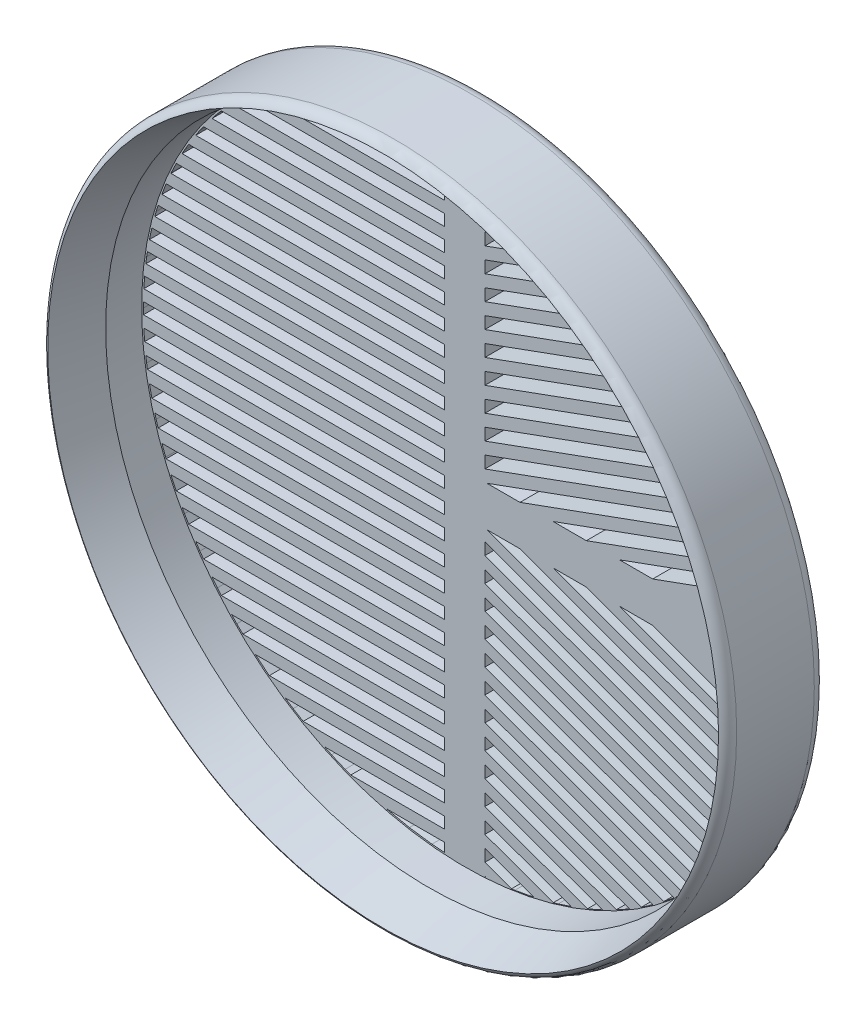
SolidWorks part; units mm, degrees
ref_plane "Front Plane" through (0, 0, 0) normal (0, 0, 1) x (1, 0, 0)
ref_plane "Top Plane" through (0, 0, 0) normal (0, 1, 0) x (1, 0, 0)
ref_plane "Right Plane" through (0, 0, 0) normal (1, 0, 0) x (0, 0, -1)
sketch "Model" plane through (0, 0, 0) normal (0, 0, 1) x (1, 0, 0)
  line L0 (75.5028, -6.5152) -> (75.5028, -6.5734)
  line L1 (75.5028, -6.5734) -> (75.6328, -6.5625)
  line L2 (75.6328, -6.5625) -> (75.5028, -6.5152)
  line L3 (60.2356, -5.0803) -> (60.3368, -5.1079)
  line L4 (60.3368, -5.1079) -> (63.7612, -5.8295)
  line L5 (63.7612, -5.8295) -> (67.2675, -6.313)
  line L6 (67.2675, -6.313) -> (69.2528, -6.4649)
  line L7 (69.2528, -6.4649) -> (69.2528, -5.0803)
  line L8 (69.2528, -5.0803) -> (60.2356, -5.0803)
  line L9 (75.5028, -2.761) -> (75.5028, -4.6381)
  line L10 (75.5028, -4.6381) -> (79.6342, -6.1418)
  line L11 (79.6342, -6.1418) -> (80.1696, -6.0715)
  line L12 (80.1696, -6.0715) -> (82.4518, -5.6634)
  line L13 (82.4518, -5.6634) -> (83.0833, -5.5201)
  line L14 (83.0833, -5.5201) -> (75.5028, -2.761)
  line L15 (50.5682, -1.5526) -> (51.6711, -2.0865)
  line L16 (51.6711, -2.0865) -> (53.7681, -2.9857)
  line L17 (53.7681, -2.9857) -> (54.6495, -3.3165)
  line L18 (54.6495, -3.3165) -> (69.2528, -3.3165)
  line L19 (69.2528, -3.3165) -> (69.2528, -1.5526)
  line L20 (69.2528, -1.5526) -> (50.5682, -1.5526)
  line L21 (75.5028, 0.9932) -> (75.5028, -0.8839)
  line L22 (75.5028, -0.8839) -> (86.1399, -4.7555)
  line L23 (86.1399, -4.7555) -> (86.9019, -4.5452)
  line L24 (86.9019, -4.5452) -> (88.9156, -3.8887)
  line L25 (88.9156, -3.8887) -> (75.5028, 0.9932)
  line L26 (44.4531, 1.9752) -> (45.6937, 1.1501)
  line L27 (45.6937, 1.1501) -> (47.2535, 0.2113)
  line L28 (47.2535, 0.2113) -> (69.2528, 0.2113)
  line L29 (69.2528, 0.2113) -> (69.2528, 1.9752)
  line L30 (69.2528, 1.9752) -> (44.4531, 1.9752)
  line L31 (75.5028, 4.7474) -> (75.5028, 2.8703)
  line L32 (75.5028, 2.8703) -> (91.4397, -2.9303)
  line L33 (91.4397, -2.9303) -> (93.2537, -2.1499)
  line L34 (93.2537, -2.1499) -> (93.7679, -1.9006)
  line L35 (93.7679, -1.9006) -> (75.5028, 4.7474)
  line L36 (39.8298, 5.503) -> (40.2413, 5.1409)
  line L37 (40.2413, 5.1409) -> (41.9862, 3.7391)
  line L38 (41.9862, 3.7391) -> (69.2528, 3.7391)
  line L39 (69.2528, 3.7391) -> (69.2528, 5.503)
  line L40 (69.2528, 5.503) -> (39.8298, 5.503)
  line L41 (75.5028, 8.5015) -> (75.5028, 6.6245)
  line L42 (75.5028, 6.6245) -> (95.9351, -0.8123)
  line L43 (95.9351, -0.8123) -> (97.244, -0.1032)
  line L44 (97.244, -0.1032) -> (97.9606, 0.3276)
  line L45 (97.9606, 0.3276) -> (75.5028, 8.5015)
  line L46 (36.1298, 9.0308) -> (36.9324, 8.1861)
  line L47 (36.9324, 8.1861) -> (37.8874, 7.2669)
  line L48 (37.8874, 7.2669) -> (69.2528, 7.2669)
  line L49 (69.2528, 7.2669) -> (69.2528, 9.0308)
  line L50 (69.2528, 9.0308) -> (36.1298, 9.0308)
  line L51 (75.5028, 12.2557) -> (75.5028, 10.3786)
  line L52 (75.5028, 10.3786) -> (99.8601, 1.5133)
  line L53 (99.8601, 1.5133) -> (101.0159, 2.2804)
  line L54 (101.0159, 2.2804) -> (101.6462, 2.7403)
  line L55 (101.6462, 2.7403) -> (75.5028, 12.2557)
  line L56 (33.081, 12.5585) -> (33.9086, 11.5147)
  line L57 (33.9086, 11.5147) -> (34.5338, 10.7947)
  line L58 (34.5338, 10.7947) -> (69.2528, 10.7947)
  line L59 (69.2528, 10.7947) -> (69.2528, 12.5585)
  line L60 (69.2528, 12.5585) -> (33.081, 12.5585)
  line L61 (75.5028, 16.0099) -> (75.5028, 14.1328)
  line L62 (75.5028, 14.1328) -> (103.3293, 4.0048)
  line L63 (103.3293, 4.0048) -> (104.5495, 4.9811)
  line L64 (104.5495, 4.9811) -> (104.918, 5.3037)
  line L65 (104.918, 5.3037) -> (75.5028, 16.0099)
  line L66 (30.5476, 16.0863) -> (31.1904, 15.106)
  line L67 (31.1904, 15.106) -> (31.7563, 14.3224)
  line L68 (31.7563, 14.3224) -> (69.2528, 14.3224)
  line L69 (69.2528, 14.3224) -> (69.2528, 16.0863)
  line L70 (69.2528, 16.0863) -> (30.5476, 16.0863)
  line L71 (28.4389, 19.6141) -> (28.7986, 18.9395)
  line L72 (28.7986, 18.9395) -> (29.4446, 17.8502)
  line L73 (29.4446, 17.8502) -> (69.2528, 17.8502)
  line L74 (69.2528, 17.8502) -> (69.2528, 19.6141)
  line L75 (69.2528, 19.6141) -> (28.4389, 19.6141)
  line L76 (75.5028, 19.7641) -> (75.5028, 17.887)
  line L77 (75.5028, 17.887) -> (106.4195, 6.6343)
  line L78 (106.4195, 6.6343) -> (107.8253, 7.9792)
  line L79 (107.8253, 7.9792) -> (107.8398, 7.9944)
  line L80 (107.8398, 7.9944) -> (75.5028, 19.7641)
  line L81 (26.6919, 23.1419) -> (26.7539, 22.9945)
  line L82 (26.7539, 22.9945) -> (27.5234, 21.378)
  line L83 (27.5234, 21.378) -> (69.2528, 21.378)
  line L84 (69.2528, 21.378) -> (69.2528, 23.1419)
  line L85 (69.2528, 23.1419) -> (26.6919, 23.1419)
  line L86 (75.5028, 23.5183) -> (75.5028, 21.6412)
  line L87 (75.5028, 21.6412) -> (109.1719, 9.3867)
  line L88 (109.1719, 9.3867) -> (109.3602, 9.5836)
  line L89 (109.3602, 9.5836) -> (110.4302, 10.8058)
  line L90 (110.4302, 10.8058) -> (75.5028, 23.5183)
  line L91 (25.2904, 26.6697) -> (25.8682, 25.0985)
  line L92 (25.8682, 25.0985) -> (25.9493, 24.9058)
  line L93 (25.9493, 24.9058) -> (69.2528, 24.9058)
  line L94 (69.2528, 24.9058) -> (69.2528, 26.6697)
  line L95 (69.2528, 26.6697) -> (25.2904, 26.6697)
  line L96 (75.5028, 27.2725) -> (75.5028, 25.3954)
  line L97 (75.5028, 25.3954) -> (111.6195, 12.25)
  line L98 (111.6195, 12.25) -> (112.2121, 12.9907)
  line L99 (112.2121, 12.9907) -> (112.7429, 13.7182)
  line L100 (112.7429, 13.7182) -> (75.5028, 27.2725)
  line L101 (24.1835, 30.1974) -> (24.3828, 29.4467)
  line L102 (24.3828, 29.4467) -> (24.703, 28.4335)
  line L103 (24.703, 28.4335) -> (69.2528, 28.4335)
  line L104 (69.2528, 28.4335) -> (69.2528, 30.1974)
  line L105 (69.2528, 30.1974) -> (24.1835, 30.1974)
  line L106 (75.5028, 31.0266) -> (75.5028, 29.1496)
  line L107 (75.5028, 29.1496) -> (113.8033, 15.2093)
  line L108 (113.8033, 15.2093) -> (114.7567, 16.6459)
  line L109 (114.7567, 16.6459) -> (114.8028, 16.7226)
  line L110 (114.8028, 16.7226) -> (75.5028, 31.0266)
  line L111 (23.348, 33.7252) -> (23.7289, 31.9613)
  line L112 (23.7289, 31.9613) -> (69.2528, 31.9613)
  line L113 (69.2528, 31.9613) -> (69.2528, 33.7252)
  line L114 (69.2528, 33.7252) -> (23.348, 33.7252)
  line L115 (75.5028, 34.7808) -> (75.5028, 32.9037)
  line L116 (75.5028, 32.9037) -> (115.7287, 18.2627)
  line L117 (115.7287, 18.2627) -> (115.9076, 18.5604)
  line L118 (115.9076, 18.5604) -> (116.5928, 19.8253)
  line L119 (116.5928, 19.8253) -> (75.5028, 34.7808)
  line L120 (22.7933, 37.253) -> (22.909, 36.2807)
  line L121 (22.909, 36.2807) -> (23.0414, 35.4891)
  line L122 (23.0414, 35.4891) -> (69.2528, 35.4891)
  line L123 (69.2528, 35.4891) -> (69.2528, 37.253)
  line L124 (69.2528, 37.253) -> (22.7933, 37.253)
  line L125 (75.5028, 38.535) -> (75.5028, 36.6579)
  line L126 (75.5028, 36.6579) -> (117.4005, 21.4084)
  line L127 (117.4005, 21.4084) -> (117.9543, 22.5507)
  line L128 (117.9543, 22.5507) -> (118.1527, 23.0117)
  line L129 (118.1527, 23.0117) -> (75.5028, 38.535)
  line L130 (96.4355, 40.3016) -> (121.0145, 31.3556)
  line L131 (121.0145, 31.3556) -> (121.4081, 33.0894)
  line L132 (121.4081, 33.0894) -> (101.5928, 40.3016)
  line L133 (101.5928, 40.3016) -> (96.4355, 40.3016)
  line L134 (86.121, 40.3016) -> (120.0409, 27.9557)
  line L135 (120.0409, 27.9557) -> (120.3496, 28.9025)
  line L136 (120.3496, 28.9025) -> (120.5548, 29.6458)
  line L137 (120.5548, 29.6458) -> (91.2782, 40.3016)
  line L138 (91.2782, 40.3016) -> (86.121, 40.3016)
  line L139 (75.8064, 40.3016) -> (118.8502, 24.6349)
  line L140 (118.8502, 24.6349) -> (119.473, 26.2854)
  line L141 (119.473, 26.2854) -> (80.9637, 40.3016)
  line L142 (80.9637, 40.3016) -> (75.8064, 40.3016)
  line L143 (22.476, 40.7808) -> (22.6017, 39.0169)
  line L144 (22.6017, 39.0169) -> (69.2528, 39.0169)
  line L145 (69.2528, 39.0169) -> (69.2528, 40.7808)
  line L146 (69.2528, 40.7808) -> (22.476, 40.7808)
  line L147 (22.4231, 44.3085) -> (22.4022, 43.4266)
  line L148 (22.4022, 43.4266) -> (22.4231, 42.5447)
  line L149 (22.4231, 42.5447) -> (69.2528, 42.5447)
  line L150 (69.2528, 42.5447) -> (69.2528, 44.3085)
  line L151 (69.2528, 44.3085) -> (22.4231, 44.3085)
  line L152 (22.6017, 47.8363) -> (22.476, 46.0724)
  line L153 (22.476, 46.0724) -> (69.2528, 46.0724)
  line L154 (69.2528, 46.0724) -> (69.2528, 47.8363)
  line L155 (69.2528, 47.8363) -> (22.6017, 47.8363)
  line L156 (23.0414, 51.3641) -> (22.909, 50.5725)
  line L157 (22.909, 50.5725) -> (22.7933, 49.6002)
  line L158 (22.7933, 49.6002) -> (69.2528, 49.6002)
  line L159 (69.2528, 49.6002) -> (69.2528, 51.3641)
  line L160 (69.2528, 51.3641) -> (23.0414, 51.3641)
  line L161 (23.7289, 54.8919) -> (23.348, 53.128)
  line L162 (23.348, 53.128) -> (69.2528, 53.128)
  line L163 (69.2528, 53.128) -> (69.2528, 54.8919)
  line L164 (69.2528, 54.8919) -> (23.7289, 54.8919)
  line L165 (121.0145, 55.4976) -> (96.4355, 46.5516)
  line L166 (96.4355, 46.5516) -> (101.5928, 46.5516)
  line L167 (101.5928, 46.5516) -> (121.4081, 53.7638)
  line L168 (121.4081, 53.7638) -> (121.0145, 55.4976)
  line L169 (24.703, 58.4197) -> (24.3828, 57.4065)
  line L170 (24.3828, 57.4065) -> (24.1835, 56.6558)
  line L171 (24.1835, 56.6558) -> (69.2528, 56.6558)
  line L172 (69.2528, 56.6558) -> (69.2528, 58.4197)
  line L173 (69.2528, 58.4197) -> (24.703, 58.4197)
  line L174 (120.0409, 58.8975) -> (86.121, 46.5516)
  line L175 (86.121, 46.5516) -> (91.2782, 46.5516)
  line L176 (91.2782, 46.5516) -> (120.5548, 57.2074)
  line L177 (120.5548, 57.2074) -> (120.3496, 57.9507)
  line L178 (120.3496, 57.9507) -> (120.0409, 58.8975)
  line L179 (25.9493, 61.9474) -> (25.8682, 61.7547)
  line L180 (25.8682, 61.7547) -> (25.2904, 60.1835)
  line L181 (25.2904, 60.1835) -> (69.2528, 60.1835)
  line L182 (69.2528, 60.1835) -> (69.2528, 61.9474)
  line L183 (69.2528, 61.9474) -> (25.9493, 61.9474)
  line L184 (118.8502, 62.2183) -> (75.8064, 46.5516)
  line L185 (75.8064, 46.5516) -> (80.9637, 46.5516)
  line L186 (80.9637, 46.5516) -> (119.473, 60.5678)
  line L187 (119.473, 60.5678) -> (118.8502, 62.2183)
  line L188 (117.4005, 65.4448) -> (75.5028, 50.1953)
  line L189 (75.5028, 50.1953) -> (75.5028, 48.3182)
  line L190 (75.5028, 48.3182) -> (118.1527, 63.8415)
  line L191 (118.1527, 63.8415) -> (117.9543, 64.3025)
  line L192 (117.9543, 64.3025) -> (117.4005, 65.4448)
  line L193 (27.5234, 65.4752) -> (26.7539, 63.8587)
  line L194 (26.7539, 63.8587) -> (26.6919, 63.7113)
  line L195 (26.6919, 63.7113) -> (69.2528, 63.7113)
  line L196 (69.2528, 63.7113) -> (69.2528, 65.4752)
  line L197 (69.2528, 65.4752) -> (27.5234, 65.4752)
  line L198 (115.7287, 68.5905) -> (75.5028, 53.9495)
  line L199 (75.5028, 53.9495) -> (75.5028, 52.0724)
  line L200 (75.5028, 52.0724) -> (116.5928, 67.0279)
  line L201 (116.5928, 67.0279) -> (115.9076, 68.2928)
  line L202 (115.9076, 68.2928) -> (115.7287, 68.5905)
  line L203 (29.4446, 69.003) -> (28.7986, 67.9137)
  line L204 (28.7986, 67.9137) -> (28.4389, 67.2391)
  line L205 (28.4389, 67.2391) -> (69.2528, 67.2391)
  line L206 (69.2528, 67.2391) -> (69.2528, 69.003)
  line L207 (69.2528, 69.003) -> (29.4446, 69.003)
  line L208 (113.8033, 71.6439) -> (75.5028, 57.7036)
  line L209 (75.5028, 57.7036) -> (75.5028, 55.8266)
  line L210 (75.5028, 55.8266) -> (114.8028, 70.1306)
  line L211 (114.8028, 70.1306) -> (114.7567, 70.2073)
  line L212 (114.7567, 70.2073) -> (113.8033, 71.6439)
  line L213 (31.7563, 72.5308) -> (31.1904, 71.7472)
  line L214 (31.1904, 71.7472) -> (30.5476, 70.7669)
  line L215 (30.5476, 70.7669) -> (69.2528, 70.7669)
  line L216 (69.2528, 70.7669) -> (69.2528, 72.5308)
  line L217 (69.2528, 72.5308) -> (31.7563, 72.5308)
  line L218 (111.6195, 74.6032) -> (75.5028, 61.4578)
  line L219 (75.5028, 61.4578) -> (75.5028, 59.5807)
  line L220 (75.5028, 59.5807) -> (112.7429, 73.135)
  line L221 (112.7429, 73.135) -> (112.2121, 73.8625)
  line L222 (112.2121, 73.8625) -> (111.6195, 74.6032)
  line L223 (34.5338, 76.0585) -> (33.9086, 75.3386)
  line L224 (33.9086, 75.3386) -> (33.081, 74.2947)
  line L225 (33.081, 74.2947) -> (69.2528, 74.2947)
  line L226 (69.2528, 74.2947) -> (69.2528, 76.0585)
  line L227 (69.2528, 76.0585) -> (34.5338, 76.0585)
  line L228 (109.1719, 77.4665) -> (75.5028, 65.212)
  line L229 (75.5028, 65.212) -> (75.5028, 63.3349)
  line L230 (75.5028, 63.3349) -> (110.4302, 76.0474)
  line L231 (110.4302, 76.0474) -> (109.3602, 77.2696)
  line L232 (109.3602, 77.2696) -> (109.1719, 77.4665)
  line L233 (37.8874, 79.5863) -> (36.9324, 78.6672)
  line L234 (36.9324, 78.6672) -> (36.1298, 77.8224)
  line L235 (36.1298, 77.8224) -> (69.2528, 77.8224)
  line L236 (69.2528, 77.8224) -> (69.2528, 79.5863)
  line L237 (69.2528, 79.5863) -> (37.8874, 79.5863)
  line L238 (106.4195, 80.219) -> (75.5028, 68.9662)
  line L239 (75.5028, 68.9662) -> (75.5028, 67.0891)
  line L240 (75.5028, 67.0891) -> (107.8398, 78.8588)
  line L241 (107.8398, 78.8588) -> (107.8253, 78.874)
  line L242 (107.8253, 78.874) -> (106.4195, 80.219)
  line L243 (103.3293, 82.8484) -> (75.5028, 72.7204)
  line L244 (75.5028, 72.7204) -> (75.5028, 70.8433)
  line L245 (75.5028, 70.8433) -> (104.918, 81.5495)
  line L246 (104.918, 81.5495) -> (104.5495, 81.8721)
  line L247 (104.5495, 81.8721) -> (103.3293, 82.8484)
  line L248 (41.9862, 83.1141) -> (40.2413, 81.7123)
  line L249 (40.2413, 81.7123) -> (39.8298, 81.3502)
  line L250 (39.8298, 81.3502) -> (69.2528, 81.3502)
  line L251 (69.2528, 81.3502) -> (69.2528, 83.1141)
  line L252 (69.2528, 83.1141) -> (41.9862, 83.1141)
  line L253 (99.8601, 85.3399) -> (75.5028, 76.4746)
  line L254 (75.5028, 76.4746) -> (75.5028, 74.5975)
  line L255 (75.5028, 74.5975) -> (101.6462, 84.1129)
  line L256 (101.6462, 84.1129) -> (101.0159, 84.5728)
  line L257 (101.0159, 84.5728) -> (99.8601, 85.3399)
  line L258 (47.2535, 86.6419) -> (45.6937, 85.7031)
  line L259 (45.6937, 85.7031) -> (44.4531, 84.878)
  line L260 (44.4531, 84.878) -> (69.2528, 84.878)
  line L261 (69.2528, 84.878) -> (69.2528, 86.6419)
  line L262 (69.2528, 86.6419) -> (47.2535, 86.6419)
  line L263 (95.9351, 87.6655) -> (75.5028, 80.2287)
  line L264 (75.5028, 80.2287) -> (75.5028, 78.3517)
  line L265 (75.5028, 78.3517) -> (97.9606, 86.5256)
  line L266 (97.9606, 86.5256) -> (97.244, 86.9564)
  line L267 (97.244, 86.9564) -> (95.9351, 87.6655)
  line L268 (91.4397, 89.7835) -> (75.5028, 83.9829)
  line L269 (75.5028, 83.9829) -> (75.5028, 82.1058)
  line L270 (75.5028, 82.1058) -> (93.7679, 88.7538)
  line L271 (93.7679, 88.7538) -> (93.2537, 89.0031)
  line L272 (93.2537, 89.0031) -> (91.4397, 89.7835)
  line L273 (54.6495, 90.1697) -> (53.7681, 89.8389)
  line L274 (53.7681, 89.8389) -> (51.6711, 88.9397)
  line L275 (51.6711, 88.9397) -> (50.5682, 88.4058)
  line L276 (50.5682, 88.4058) -> (69.2528, 88.4058)
  line L277 (69.2528, 88.4058) -> (69.2528, 90.1697)
  line L278 (69.2528, 90.1697) -> (54.6495, 90.1697)
  line L279 (86.1399, 91.6087) -> (75.5028, 87.7371)
  line L280 (75.5028, 87.7371) -> (75.5028, 85.86)
  line L281 (75.5028, 85.86) -> (88.9156, 90.7419)
  line L282 (88.9156, 90.7419) -> (86.9019, 91.3984)
  line L283 (86.9019, 91.3984) -> (86.1399, 91.6087)
  line L284 (79.6342, 92.995) -> (75.5028, 91.4913)
  line L285 (75.5028, 91.4913) -> (75.5028, 89.6142)
  line L286 (75.5028, 89.6142) -> (83.0833, 92.3733)
  line L287 (83.0833, 92.3733) -> (82.4518, 92.5166)
  line L288 (82.4518, 92.5166) -> (80.1696, 92.9247)
  line L289 (80.1696, 92.9247) -> (79.6342, 92.995)
  line L290 (69.2528, 93.3181) -> (67.2675, 93.1662)
  line L291 (67.2675, 93.1662) -> (63.7612, 92.6827)
  line L292 (63.7612, 92.6827) -> (60.3368, 91.9611)
  line L293 (60.3368, 91.9611) -> (60.2356, 91.9335)
  line L294 (60.2356, 91.9335) -> (69.2528, 91.9335)
  line L295 (69.2528, 91.9335) -> (69.2528, 93.3181)
  line L296 (75.5028, 93.4266) -> (75.5028, 93.3684)
  line L297 (75.5028, 93.3684) -> (75.6328, 93.4157)
  line L298 (75.6328, 93.4157) -> (75.5028, 93.4266)
  line L299 (72.3778, 105.9267) -> (75.5941, 105.8453)
  line L300 (75.5941, 105.8453) -> (78.7681, 105.604)
  line L301 (78.7681, 105.604) -> (81.896, 105.2065)
  line L302 (81.896, 105.2065) -> (84.9738, 104.6569)
  line L303 (84.9738, 104.6569) -> (87.9976, 103.959)
  line L304 (87.9976, 103.959) -> (90.9634, 103.1168)
  line L305 (90.9634, 103.1168) -> (93.8674, 102.1342)
  line L306 (93.8674, 102.1342) -> (96.7057, 101.0151)
  line L307 (96.7057, 101.0151) -> (99.4742, 99.7635)
  line L308 (99.4742, 99.7635) -> (102.1691, 98.3832)
  line L309 (102.1691, 98.3832) -> (107.3222, 95.2526)
  line L310 (107.3222, 95.2526) -> (112.1337, 91.6547)
  line L311 (112.1337, 91.6547) -> (116.572, 87.6208)
  line L312 (116.572, 87.6208) -> (120.6059, 83.1824)
  line L313 (120.6059, 83.1824) -> (124.2039, 78.371)
  line L314 (124.2039, 78.371) -> (127.3345, 73.2178)
  line L315 (127.3345, 73.2178) -> (128.7147, 70.523)
  line L316 (128.7147, 70.523) -> (129.9663, 67.7544)
  line L317 (129.9663, 67.7544) -> (131.0854, 64.9162)
  line L318 (131.0854, 64.9162) -> (132.068, 62.0122)
  line L319 (132.068, 62.0122) -> (132.9102, 59.0463)
  line L320 (132.9102, 59.0463) -> (133.6081, 56.0225)
  line L321 (133.6081, 56.0225) -> (134.1577, 52.9447)
  line L322 (134.1577, 52.9447) -> (134.5552, 49.8169)
  line L323 (134.5552, 49.8169) -> (134.7966, 46.6428)
  line L324 (134.7966, 46.6428) -> (134.8779, 43.4266)
  line L325 (134.8779, 43.4266) -> (134.7966, 40.2104)
  line L326 (134.7966, 40.2104) -> (134.5552, 37.0363)
  line L327 (134.5552, 37.0363) -> (134.1577, 33.9085)
  line L328 (134.1577, 33.9085) -> (133.6081, 30.8307)
  line L329 (133.6081, 30.8307) -> (132.9102, 27.8069)
  line L330 (132.9102, 27.8069) -> (132.068, 24.841)
  line L331 (132.068, 24.841) -> (131.0854, 21.937)
  line L332 (131.0854, 21.937) -> (129.9663, 19.0988)
  line L333 (129.9663, 19.0988) -> (128.7147, 16.3302)
  line L334 (128.7147, 16.3302) -> (127.3345, 13.6354)
  line L335 (127.3345, 13.6354) -> (124.2039, 8.4822)
  line L336 (124.2039, 8.4822) -> (120.6059, 3.6708)
  line L337 (120.6059, 3.6708) -> (116.572, -0.7676)
  line L338 (116.572, -0.7676) -> (112.1337, -4.8015)
  line L339 (112.1337, -4.8015) -> (107.3222, -8.3994)
  line L340 (107.3222, -8.3994) -> (102.1691, -11.53)
  line L341 (102.1691, -11.53) -> (99.4742, -12.9103)
  line L342 (99.4742, -12.9103) -> (96.7057, -14.1619)
  line L343 (96.7057, -14.1619) -> (93.8674, -15.281)
  line L344 (93.8674, -15.281) -> (90.9634, -16.2636)
  line L345 (90.9634, -16.2636) -> (87.9976, -17.1058)
  line L346 (87.9976, -17.1058) -> (84.9738, -17.8037)
  line L347 (84.9738, -17.8037) -> (81.896, -18.3533)
  line L348 (81.896, -18.3533) -> (78.7681, -18.7508)
  line L349 (78.7681, -18.7508) -> (75.5941, -18.9921)
  line L350 (75.5941, -18.9921) -> (72.3778, -19.0734)
  line L351 (72.3778, -19.0734) -> (69.1616, -18.9921)
  line L352 (69.1616, -18.9921) -> (65.9876, -18.7508)
  line L353 (65.9876, -18.7508) -> (62.8597, -18.3533)
  line L354 (62.8597, -18.3533) -> (59.7819, -17.8037)
  line L355 (59.7819, -17.8037) -> (56.7581, -17.1058)
  line L356 (56.7581, -17.1058) -> (53.7922, -16.2636)
  line L357 (53.7922, -16.2636) -> (50.8882, -15.281)
  line L358 (50.8882, -15.281) -> (48.05, -14.1619)
  line L359 (48.05, -14.1619) -> (45.2815, -12.9103)
  line L360 (45.2815, -12.9103) -> (42.5866, -11.53)
  line L361 (42.5866, -11.53) -> (37.4335, -8.3994)
  line L362 (37.4335, -8.3994) -> (32.622, -4.8015)
  line L363 (32.622, -4.8015) -> (28.1836, -0.7676)
  line L364 (28.1836, -0.7676) -> (24.1498, 3.6708)
  line L365 (24.1498, 3.6708) -> (20.5518, 8.4822)
  line L366 (20.5518, 8.4822) -> (17.4212, 13.6354)
  line L367 (17.4212, 13.6354) -> (16.041, 16.3302)
  line L368 (16.041, 16.3302) -> (14.7893, 19.0988)
  line L369 (14.7893, 19.0988) -> (13.6703, 21.937)
  line L370 (13.6703, 21.937) -> (12.6877, 24.841)
  line L371 (12.6877, 24.841) -> (11.8454, 27.8069)
  line L372 (11.8454, 27.8069) -> (11.1476, 30.8307)
  line L373 (11.1476, 30.8307) -> (10.5979, 33.9085)
  line L374 (10.5979, 33.9085) -> (10.2005, 37.0363)
  line L375 (10.2005, 37.0363) -> (9.9591, 40.2104)
  line L376 (9.9591, 40.2104) -> (9.8778, 43.4266)
  line L377 (9.8778, 43.4266) -> (9.9591, 46.6428)
  line L378 (9.9591, 46.6428) -> (10.2005, 49.8169)
  line L379 (10.2005, 49.8169) -> (10.5979, 52.9447)
  line L380 (10.5979, 52.9447) -> (11.1476, 56.0225)
  line L381 (11.1476, 56.0225) -> (11.8454, 59.0463)
  line L382 (11.8454, 59.0463) -> (12.6877, 62.0122)
  line L383 (12.6877, 62.0122) -> (13.6703, 64.9162)
  line L384 (13.6703, 64.9162) -> (14.7893, 67.7544)
  line L385 (14.7893, 67.7544) -> (16.041, 70.523)
  line L386 (16.041, 70.523) -> (17.4212, 73.2178)
  line L387 (17.4212, 73.2178) -> (20.5518, 78.371)
  line L388 (20.5518, 78.371) -> (24.1498, 83.1824)
  line L389 (24.1498, 83.1824) -> (28.1836, 87.6208)
  line L390 (28.1836, 87.6208) -> (32.622, 91.6547)
  line L391 (32.622, 91.6547) -> (37.4335, 95.2526)
  line L392 (37.4335, 95.2526) -> (42.5866, 98.3832)
  line L393 (42.5866, 98.3832) -> (45.2815, 99.7635)
  line L394 (45.2815, 99.7635) -> (48.05, 101.0151)
  line L395 (48.05, 101.0151) -> (50.8882, 102.1342)
  line L396 (50.8882, 102.1342) -> (53.7922, 103.1168)
  line L397 (53.7922, 103.1168) -> (56.7581, 103.959)
  line L398 (56.7581, 103.959) -> (59.7819, 104.6569)
  line L399 (59.7819, 104.6569) -> (62.8597, 105.2065)
  line L400 (62.8597, 105.2065) -> (65.9876, 105.604)
  line L401 (65.9876, 105.604) -> (69.1616, 105.8453)
  line L402 (69.1616, 105.8453) -> (72.3778, 105.9267)
extrude "Boss-Extrude1" add sketch "Model" along normal blind 3
sketch "Sketch2" plane through (0, 0, 3) normal (0, 0, 1) x (1, 0, 0)
  line L0 (86.121, 46.5516) -> (86.121, 40.3016) construction
  line L1 (86.121, 43.4266) -> (63.7612, 43.4266) construction
  line L2 (75.5028, 89.6142) -> (69.2528, 89.6142) construction
  line L3 (69.2528, 88.4058) -> (69.2528, 90.1697) construction
  line L4 (72.3778, 89.6142) -> (72.3778, 34.5611) construction
  circle A0 centre (72.3778, 43.4266) radius 50.25
  circle A1 centre (72.3778, 43.4266) radius 53.25
  point P13 (72.3778, 43.4266)
  dimension "D1" = 100.5
  dimension "D2" = 3
extrude "Boss-Extrude2" add sketch "Sketch2" along normal blind 12.7
sketch "Sketch3" plane through (0, 0, 3) normal (0, 0, 1) x (1, 0, 0)
  circle A0 centre (72.3778, 43.4266) radius 53.25
  circle A1 centre (72.3778, 43.4266) radius 78.65
  circle A2 centre (72.3778, 43.4266) radius 53.25 construction
  dimension "D1" = 25.4
extrude "Cut-Extrude1" cut sketch "Sketch3" against normal through all
chamfer "Chamfer1" distance 1.905 angle 75 1 edges at (122.6278, 43.4266, 15.7) first distance on face at (125.6278, 43.4266, 15.7)
fillet "Fillet1" radius 1.905 2 edges at (125.6278, 43.4266, 0) (125.6278, 43.4266, 15.7)
chamfer "Chamfer2" [suppressed] distance 0.762 angle 75
